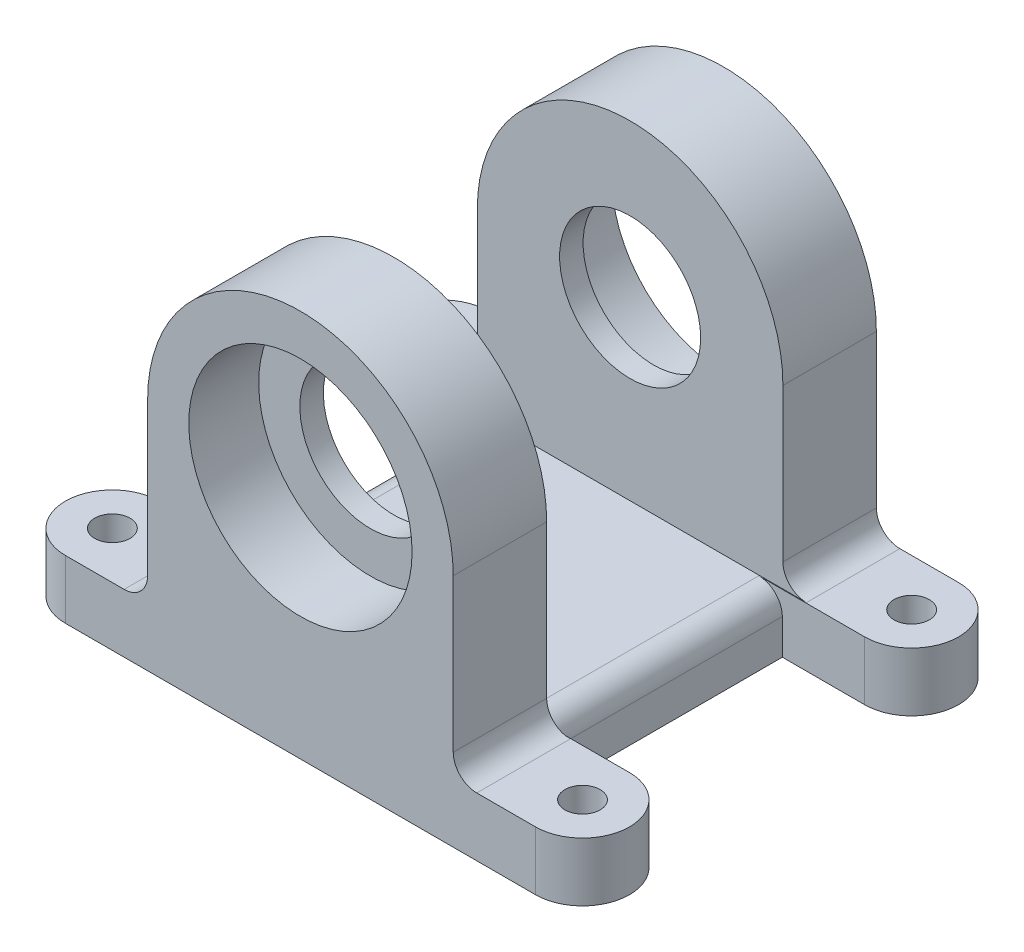
SolidWorks part; units mm, degrees
ref_plane "Alzado" through (0, 0, 0) normal (0, 0, 1) x (1, 0, 0)
ref_plane "Planta" through (0, 0, 0) normal (0, 1, 0) x (1, 0, 0)
ref_plane "Vista lateral" through (0, 0, 0) normal (1, 0, 0) x (0, 0, -1)
sketch "Croquis1" plane through (0, 0, 0) normal (0, 0, 1) x (1, 0, 0)
  line L0 (0, 0) -> (0, 17.6859) construction
  line L1 (0, 0) -> (-25.4426, 0) construction
  line L2 (-13, 0) -> (-13, -20)
  line L3 (-13, -20) -> (13, -20)
  line L4 (13, -20) -> (13, 0)
  circle A0 centre (0, 0) radius 9.5
  arc A1 (13, 0) -> (-13, 0) centre (0, 0) ccw
  dimension "D1" = 19
  dimension "D2" = 13
  dimension "D3" = 20
extrude "Saliente-Extruir1" add sketch "Croquis1" along normal blind 36
sketch "Croquis2" plane through (13, 0, 0) normal (1, 0, 0) x (0, 0, -1)
  line L0 (-18, -20) -> (-18, -29.3415) construction
  line L1 (-36, -20) -> (0, -20) construction
  line L4 (0, 13) -> (-36, 13) construction
  line L5 (-7.95, 13) -> (-28.05, 13)
  line L7 (-28.05, 13) -> (-28.05, -15)
  line L8 (-28.05, -15) -> (-7.95, -15)
  line L9 (-7.95, -15) -> (-7.95, 13)
  dimension "D1" = 20.1
  dimension "D2" = 5
extrude "Cortar-Extruir2" cut sketch "Croquis2" against normal through all
sketch "Croquis3" plane through (0, 0, 28.05) normal (0, 0, -1) x (-1, 0, 0)
  circle A0 centre (0, 0) radius 9.5
  circle A1 centre (0, 0) radius 6
  dimension "D1" = 19
  dimension "D2" = 12
extrude "Saliente-Extruir2" add sketch "Croquis3" against normal blind 2
sketch "Croquis4" plane through (0, 0, 7.95) normal (0, 0, 1) x (1, 0, 0)
  circle A0 centre (0, 0) radius 9.5 construction
  circle A1 centre (0, 0) radius 9.5
  circle A2 centre (0, 0) radius 6 construction
  circle A3 centre (0, 0) radius 6
extrude "Saliente-Extruir3" add sketch "Croquis4" against normal blind 2
sketch "Croquis5" plane through (0, -20, 0) normal (0, -1, 0) x (1, 0, 0)
  line L0 (13, 36) -> (20, 36)
  line L1 (20, 28) -> (13, 28)
  line L2 (13, 36) -> (13, 0) construction
  line L3 (13, 28) -> (13, 36)
  line L4 (13, 0) -> (20, 0)
  line L5 (20, 8) -> (13, 8)
  line L6 (13, 8) -> (13, 0)
  line L7 (0, 0) -> (0, -17.9347) construction
  line L8 (-13, 0) -> (-20, 0)
  line L9 (-20, 8) -> (-13, 8)
  line L10 (-13, 8) -> (-13, 0)
  line L11 (-13, 28) -> (-13, 36)
  line L12 (-13, 36) -> (-20, 36)
  line L13 (-20, 28) -> (-13, 28)
  arc A0 (20, 36) -> (20, 28) centre (20, 32) cw
  arc A1 (20, 0) -> (20, 8) centre (20, 4) ccw
  arc A2 (-20, 0) -> (-20, 8) centre (-20, 4) cw
  arc A3 (-20, 36) -> (-20, 28) centre (-20, 32) ccw
  dimension "D1" = 7
  dimension "D2" = 4
  dimension "D4" = 4
  dimension "D3" = 7
extrude "Saliente-Extruir4" add sketch "Croquis5" against normal blind 5
sketch "Croquis6" plane through (0, -20, 0) normal (0, -1, 0) x (1, 0, 0)
  circle A0 centre (-20, 32) radius 1.5
  circle A1 centre (20, 32) radius 1.5
  circle A2 centre (-20, 4) radius 1.5
  circle A3 centre (20, 4) radius 1.5
  dimension "D1" = 3
  dimension "D2" = 3
  dimension "D3" = 3
  dimension "D4" = 3
extrude "Cortar-Extruir3" cut sketch "Croquis6" against normal through all
fillet "Redondeo1" [suppressed] radius 3
fillet "Redondeo2" [suppressed] radius 3
fillet "Redondeo3" radius 2 6 edges at (-13, -15, 32.025) (-13, -15, 3.975) (-13, -15, 18) (13, -15, 3.975) (13, -15, 18) (13, -15, 32.025)
